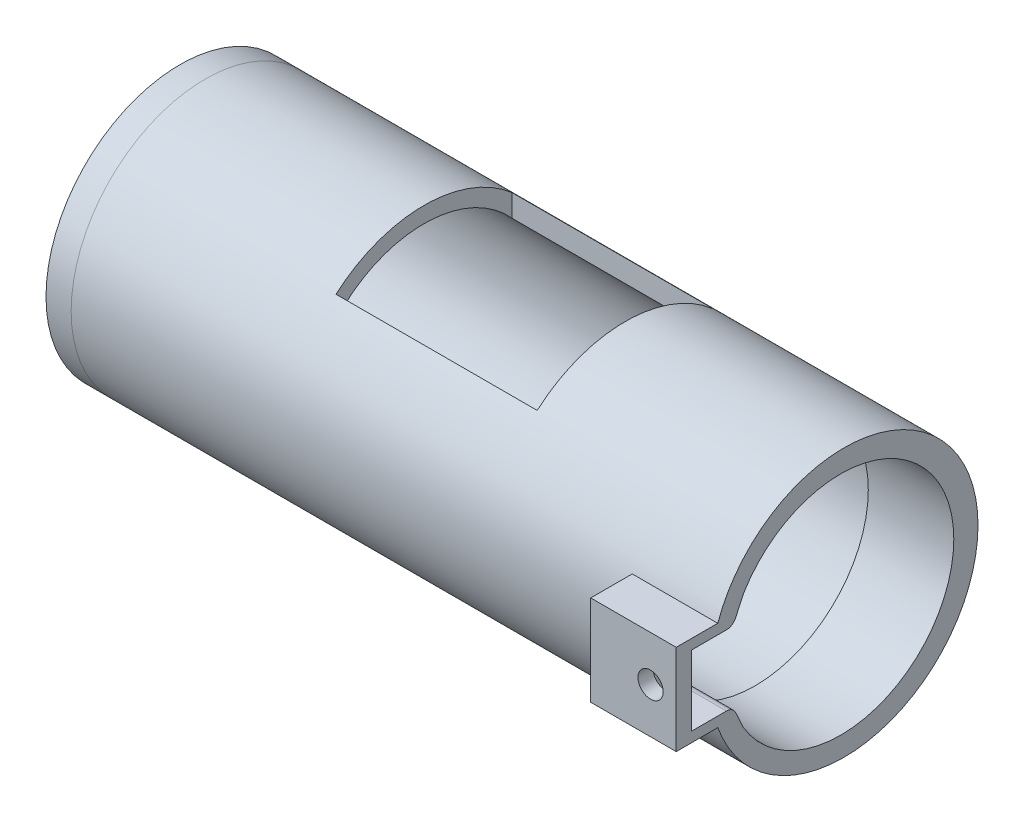
SolidWorks part; units mm, degrees
ref_plane "Front Plane" through (0, 0, 0) normal (0, 0, 1) x (1, 0, 0)
ref_plane "Top Plane" through (0, 0, 0) normal (0, 1, 0) x (1, 0, 0)
ref_plane "Right Plane" through (0, 0, 0) normal (1, 0, 0) x (0, 0, -1)
sketch "Sketch2" plane through (0, 0, 0) normal (1, 0, 0) x (0, 0, -1)
  line L0 (-54.6867, 24.5089) -> (-52.485, 24.5089) construction
  line L2 (-62.835, 13.0089) -> (-32.485, 13.0089) construction
  line L3 (-62.835, 13.0089) -> (-32.485, 13.0089) construction
  line L17 (-52.485, 24.5089) -> (-52.485, 1.5089) construction
  line L19 (-62.835, 19.9939) -> (-62.835, 6.0239)
  line L20 (-62.835, 6.0239) -> (-55.8441, 6.0239)
  line L21 (-54.0273, 4.8601) -> (-52.485, 1.5089)
  line L22 (-52.485, 1.5089) -> (-48.985, 1.0089) construction
  line L23 (-48.985, 1.0089) -> (-47.0768, 2.4695) construction
  line L24 (-47.0956, 23.5627) -> (-48.985, 25.0089) construction
  line L25 (-48.985, 25.0089) -> (-52.485, 24.5089) construction
  line L26 (-52.485, 24.5089) -> (-54.0273, 21.1578)
  line L27 (-55.8441, 19.9939) -> (-62.835, 19.9939)
  line L28 (-65.835, 21.9939) -> (-65.835, 4.0239)
  line L29 (-65.835, 4.0239) -> (-57.5747, 4.0239)
  line L31 (-65.835, 21.9939) -> (-57.5747, 21.9939)
  circle A1 centre (-32.485, 13.0089) radius 21 construction
  arc A2 (-52.485, 24.5089) -> (-52.485, 1.5089) centre (-33.146, 13.0089) cw
  arc A5 (-54.0273, 4.8601) -> (-55.8441, 6.0239) centre (-55.8441, 4.0239) ccw
  arc A7 (-55.8441, 19.9939) -> (-54.0273, 21.1578) centre (-55.8441, 21.9939) ccw
  arc A12 (-57.5747, 4.0239) -> (-57.5747, 21.9939) centre (-32.485, 13.0089) ccw
  dimension "D1" = 42
  dimension "D4" = 2
  dimension "D7" = 30.35
  dimension "D8" = 22.5
  dimension "D10" = 30.35
  dimension "D12" = 53.3
  dimension "D5" = 2
  dimension "D6" = 3
extrude "Boss-Extrude4" add sketch "Sketch2" against normal blind 10.2
sketch "Sketch6" plane through (0, 0, 0) normal (0, 0, 1) x (1, 0, 0)
  line L0 (-10.2, 21.9939) -> (0, 4.0239) construction
  circle A2 centre (-5.1, 13.0089) radius 2.5
  dimension "D2" = 5
extrude "Cut-Extrude2" cut sketch "Sketch6" against normal blind 3 from surface starting at face at (-5.1, 13.0089, 65.835)
sketch "Sketch8" plane through (0, 0, 0) normal (1, 0, 0) x (0, 0, -1)
  line L12 (-54.0273, 4.8601) -> (-52.485, 1.5089) construction
  line L13 (-54.0273, 4.8601) -> (-52.485, 1.5089)
  line L15 (-57.5747, 21.9939) -> (-65.835, 21.9939)
  line L16 (-65.835, 21.9939) -> (-65.835, 4.0239)
  line L17 (-65.835, 4.0239) -> (-57.5747, 4.0239)
  line L20 (-57.5747, 21.9939) -> (-65.835, 21.9939)
  line L21 (-65.835, 21.9939) -> (-65.835, 4.0239)
  line L22 (-65.835, 4.0239) -> (-57.5747, 4.0239)
  line L25 (-52.485, 24.5089) -> (-54.0273, 21.1578) construction
  line L27 (-52.485, 24.5089) -> (-54.0273, 21.1578)
  arc A11 (-54.0273, 4.8601) -> (-55.8441, 6.0239) centre (-55.8441, 4.0239) ccw construction
  arc A13 (-52.485, 1.5089) -> (-52.485, 24.5089) centre (-33.146, 13.0089) ccw construction
  arc A14 (-57.5747, 4.0239) -> (-57.5747, 21.9939) centre (-32.485, 13.0089) ccw
  arc A15 (-57.5747, 4.0239) -> (-57.5747, 21.9939) centre (-32.485, 13.0089) ccw
  arc A20 (-52.485, 1.5089) -> (-52.485, 24.5089) centre (-33.146, 13.0089) ccw
  arc A21 (-55.8441, 19.9939) -> (-54.0273, 21.1578) centre (-55.8441, 21.9939) ccw construction
  arc A23 (-54.0273, 21.1578) -> (-54.0273, 4.8601) centre (-36.3205, 13.0089) ccw
  dimension "D1" = 0
extrude "Boss-Extrude2" add sketch "Sketch8" against normal blind 6.8 from surface starting at face at (-10.2, 13.0089, 51.0254)
sketch "Sketch9" plane through (0, 0, 0) normal (1, 0, 0) x (0, 0, -1)
  line L0 (-62.835, 13.0089) -> (-32.485, 13.0089) construction
  line L5 (-62.835, 19.9939) -> (-62.835, 6.0239) construction
  circle A5 centre (-32.485, 13.0089) radius 23.5
  circle A6 centre (-32.485, 13.0089) radius 26.65
  dimension "D2" = 47
  dimension "D3" = 53.3
  dimension "D1" = 30.35
extrude "Boss-Extrude3" add sketch "Sketch9" against normal blind 110 from offset 17 offset against normal yes
sketch "Sketch10" plane through (0, 0, 0) normal (1, 0, 0) x (0, 0, -1)
  point P5 (-31.4084, 12.5051)
extrude "Boss-Extrude5" add sketch "Sketch9<2>" against normal blind 5 from surface separate body starting at face at (-127, 13.0089, 8.985)
sketch "Sketch9<2>" plane through (0, 0, 0) normal (1, 0, 0) x (0, 0, -1) same geometry as "Sketch9"
sketch "Sketch11" plane through (0, 0, 0) normal (0, 1, 0) x (1, 0, 0)
  line L0 (-127, -59.135) -> (0, -5.835) construction
  line L2 (-83.5, -14.985) -> (-43.5, -14.985)
  line L3 (-83.5, -14.985) -> (-83.5, -49.985)
  line L4 (-83.5, -49.985) -> (-43.5, -49.985)
  line L5 (-43.5, -14.985) -> (-43.5, -49.985)
  line L6 (-83.5, -14.985) -> (-43.5, -49.985) construction
  line L7 (-83.5, -49.985) -> (-43.5, -14.985) construction
  point P4 (-63.5, -32.485)
  point P5 (-63.5, -32.485)
  point P10 (-83.8379, -15.3111)
  point P11 (0, 0)
  dimension "D1" = 35
  dimension "D2" = 40
extrude "Cut-Extrude3" cut sketch "Sketch11" against normal through all both and the other way through all
